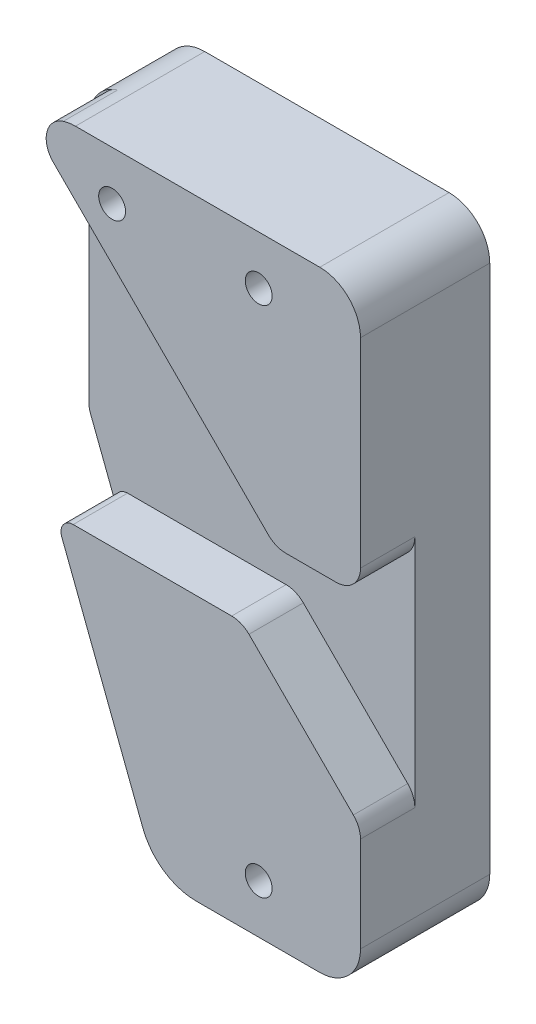
SolidWorks part; units mm, degrees
ref_plane "Front Plane" through (0, 0, 0) normal (0, 0, 1) x (1, 0, 0)
ref_plane "Top Plane" through (0, 0, 0) normal (0, 1, 0) x (1, 0, 0)
ref_plane "Right Plane" through (0, 0, 0) normal (1, 0, 0) x (0, 0, -1)
sketch "Sketch1" plane through (0, 0, 0) normal (0, 0, 1) x (1, 0, 0)
  line L0 (12.5, 69) -> (12.5, 6) construction
  line L1 (0, 0) -> (25, 0)
  line L2 (0, 0) -> (0, 75)
  line L3 (0, 75) -> (25, 75)
  line L4 (25, 0) -> (25, 75)
  line L6 (0, 75) -> (-15, 75)
  line L7 (0, 75) -> (0, 37.5)
  line L8 (0, 37.5) -> (-15, 37.5)
  line L9 (-15, 75) -> (-15, 37.5)
  circle A0 centre (12.5, 69) radius 1.5
  circle A1 centre (12.5, 6) radius 1.5
  circle A2 centre (12.5, 37.5) radius 1.5
  dimension "D3" = 3
  dimension "D4" = 3
  dimension "D7" = 3
  dimension "D1" = 75
  dimension "D2" = 25
  dimension "D5" = 6
  dimension "D6" = 6
  dimension "D8" = 0
  dimension "D9" = 12.5
  dimension "D10" = 15
extrude "Boss-Extrude1" add sketch "Sketch1" along normal blind 2.85 contours L6 L9 L8 L2 | L1 L4 L3 L2 A0 A2 A1 region at (0.7906, 18.75, 0) region at (-7.5, 56.25, 0)
fillet "Fillet1" radius 5 5 edges at (25, 0, 1.425) (0, 0, 1.425) (25, 75, 1.425) (-15, 75, 1.425) (0, 37.5, 1.425)
fillet "Fillet2" radius 2 1 edges at (-15, 37.5, 1.425)
sketch "Sketch5" plane through (0, 0, 2.85) normal (0, 0, 1) x (1, 0, 0)
  line L0 (0, 25) -> (25, 50)
  line L3 (-17.5, 42.5) -> (42.5, 42.5)
  line L4 (42.5, 32.5) -> (42.5, 42.5)
  line L5 (-0.8417, 35.2764) -> (42.5, 42.5) construction
  line L6 (-17.5, 42.5) -> (42.5, 32.5) construction
  line L7 (0, 17.9289) -> (25, 42.9289)
  line L8 (0, 32.0711) -> (21.4645, 53.5355)
  line L9 (-20.8226, 11.2484) -> (21.4645, 53.5355) construction
  line L10 (-17.2871, 7.7129) -> (25, 50) construction
  line L11 (-13.7516, 4.1774) -> (28.5355, 46.4645) construction
  line L12 (21.4645, 53.5355) -> (25, 57.0711)
  line L13 (-15, 70) -> (-15, 39.5)
  line L14 (-13, 37.5) -> (-5, 37.5)
  line L15 (0, 32.5) -> (0, 5)
  line L16 (5, 0) -> (20, 0)
  line L17 (25, 5) -> (25, 70)
  line L18 (20, 75) -> (-10, 75)
  line L19 (-15, 70) -> (-15, 39.5)
  line L20 (-13, 37.5) -> (-5, 37.5)
  line L21 (0, 32.5) -> (0, 5)
  line L22 (5, 0) -> (20, 0)
  line L23 (25, 5) -> (25, 70)
  line L24 (20, 75) -> (-10, 75)
  line L25 (42.5, 32.5) -> (14.5711, 32.5)
  arc A6 (-15, 39.5) -> (-13, 37.5) centre (-13, 39.5) ccw
  arc A7 (0, 32.5) -> (-5, 37.5) centre (-5, 32.5) ccw
  arc A8 (0, 5) -> (5, 0) centre (5, 5) ccw
  arc A9 (20, 0) -> (25, 5) centre (20, 5) ccw
  arc A10 (25, 70) -> (20, 75) centre (20, 70) ccw
  arc A11 (-10, 75) -> (-15, 70) centre (-10, 70) ccw
  arc A12 (-15, 39.5) -> (-13, 37.5) centre (-13, 39.5) ccw
  arc A13 (0, 32.5) -> (-5, 37.5) centre (-5, 32.5) ccw
  arc A14 (0, 5) -> (5, 0) centre (5, 5) ccw
  arc A15 (20, 0) -> (25, 5) centre (20, 5) ccw
  arc A16 (25, 70) -> (20, 75) centre (20, 70) ccw
  arc A17 (-10, 75) -> (-15, 70) centre (-10, 70) ccw
  point P0 (12.5, 37.5)
  point P9 (12.5, 37.5)
  line M2 (-15, 70) -> (-15, 39.5)
  line M6 (0, 32.5) -> (0, 5)
  arc M7 (0, 5) -> (5, 0) centre (5, 5) ccw
  line M8 (5, 0) -> (20, 0)
  arc M9 (20, 0) -> (25, 5) centre (20, 5) ccw
  line M10 (25, 5) -> (25, 70)
  arc M11 (25, 70) -> (20, 75) centre (20, 70) ccw
  line M12 (20, 75) -> (-10, 75)
  arc M13 (-10, 75) -> (-15, 70) centre (-10, 70) ccw
  circle M15 centre (12.5, 6) radius 1.5
  circle M16 centre (12.5, 69) radius 1.5
  dimension "D3" = 0
  dimension "D4" = 5
  dimension "D5" = 5
extrude "Boss-Extrude2" add sketch "Sketch5" along normal blind 3.5 contours L8 L12 L3 M10 M11 M12 M13 M2 M16 | L25 L7 M10 M6 M7 M8 M9 M15 region at (13.6784, 14.8345, 2.85) region at (3.588, 59.5787, 2.85)
fillet "Fillet3" radius 3.5 2 edges at (14.5711, 32.5, 4.6) (10.4289, 42.5, 4.6)
fillet "Fillet4" radius 2 1 edges at (-15, 42.5, 4.6)
fillet "Fillet5" radius 2 3 edges at (0, 17.9289, 4.6) (25, 32.5, 4.6) (25, 57.0711, 4.6)
sketch "Sketch6" plane through (0, 0, 6.35) normal (0, 0, 1) x (1, 0, 0)
  circle A0 centre (-5.5, 69) radius 1.5
  circle A1 centre (12.5, 69) radius 1.5 construction
  dimension "D1" = 3
  dimension "D2" = 18
extrude "Cut-Extrude1" cut sketch "Sketch6" against normal blind 10
sketch "Sketch8" plane through (0, 0, 0) normal (0, 0, -1) x (-1, 0, 0)
  line L6 (5, 37.5) -> (13, 37.5)
  line L7 (15, 39.5) -> (15, 70)
  line L8 (10, 75) -> (-20, 75)
  line L9 (-25, 70) -> (-25, 5)
  line L10 (-20, 0) -> (-5, 0)
  line L11 (0, 5) -> (0, 32.5)
  line L12 (5, 37.5) -> (13, 37.5)
  line L13 (15, 39.5) -> (15, 70)
  line L14 (10, 75) -> (-20, 75)
  line L15 (-25, 70) -> (-25, 5)
  line L16 (-20, 0) -> (-5, 0)
  line L17 (0, 5) -> (0, 32.5)
  arc A6 (13, 37.5) -> (15, 39.5) centre (13, 39.5) ccw
  arc A7 (15, 70) -> (10, 75) centre (10, 70) ccw
  arc A8 (-20, 75) -> (-25, 70) centre (-20, 70) ccw
  arc A9 (-25, 5) -> (-20, 0) centre (-20, 5) ccw
  arc A10 (-5, 0) -> (0, 5) centre (-5, 5) ccw
  arc A11 (5, 37.5) -> (0, 32.5) centre (5, 32.5) ccw
  arc A12 (13, 37.5) -> (15, 39.5) centre (13, 39.5) ccw
  arc A13 (15, 70) -> (10, 75) centre (10, 70) ccw
  arc A14 (-20, 75) -> (-25, 70) centre (-20, 70) ccw
  arc A15 (-25, 5) -> (-20, 0) centre (-20, 5) ccw
  arc A16 (-5, 0) -> (0, 5) centre (-5, 5) ccw
  arc A17 (5, 37.5) -> (0, 32.5) centre (5, 32.5) ccw
  circle M13 centre (5.5, 69) radius 1.5
  line M14 (5, 37.5) -> (13, 37.5)
  arc M15 (13, 37.5) -> (15, 39.5) centre (13, 39.5) ccw
  line M16 (15, 39.5) -> (15, 70)
  arc M17 (15, 70) -> (10, 75) centre (10, 70) ccw
  line M18 (10, 75) -> (-20, 75)
  arc M19 (-20, 75) -> (-25, 70) centre (-20, 70) ccw
  line M20 (-25, 70) -> (-25, 5)
  arc M21 (-25, 5) -> (-20, 0) centre (-20, 5) ccw
  line M22 (-20, 0) -> (-5, 0)
  arc M23 (-5, 0) -> (0, 5) centre (-5, 5) ccw
  line M24 (0, 5) -> (0, 32.5)
  arc M25 (0, 32.5) -> (5, 37.5) centre (5, 32.5) cw
  circle M26 centre (-12.5, 37.5) radius 1.5
  circle M27 centre (-12.5, 6) radius 1.5
  circle M28 centre (-12.5, 69) radius 1.5
  dimension "D1" = 0
extrude "Boss-Extrude3" add sketch "Sketch8" along normal blind 6.35 contours M25 M14 M15 M16 M17 M18 M19 M20 M21 M22 M23 M24 M27 M28 M26 M13 region at (7.8634, 41.813, 0)
sketch "Sketch9" plane through (0, 0, 6.35) normal (0, 0, 1) x (1, 0, 0)
  line L0 (13.5459, 31.4749) -> (0.5858, 18.5147) construction
  line L1 (0, 17.1005) -> (0, 5) construction
  line L2 (5, 0) -> (20, 0) construction
  line L3 (25, 5) -> (25, 30.5) construction
  line L4 (23, 32.5) -> (16.0208, 32.5) construction
  line L5 (11.4541, 43.5251) -> (24.4142, 56.4853) construction
  line L6 (25, 57.8995) -> (25, 70) construction
  line L7 (20, 75) -> (-10, 75) construction
  line L8 (-15, 70) -> (-15, 44.5) construction
  line L9 (-13, 42.5) -> (8.9792, 42.5) construction
  line L10 (13.5459, 31.4749) -> (0.5858, 18.5147)
  line L11 (0, 17.1005) -> (0, 5)
  line L12 (5, 0) -> (20, 0)
  line L13 (25, 5) -> (25, 30.5)
  line L14 (23, 32.5) -> (16.0208, 32.5)
  line L15 (11.4541, 43.5251) -> (24.4142, 56.4853)
  line L16 (25, 57.8995) -> (25, 70)
  line L17 (20, 75) -> (-10, 75)
  line L18 (-15, 70) -> (-15, 44.5)
  line L19 (-13, 42.5) -> (8.9792, 42.5)
  arc A0 (0.5858, 18.5147) -> (0, 17.1005) centre (2, 17.1005) ccw construction
  arc A1 (0, 5) -> (5, 0) centre (5, 5) ccw construction
  arc A2 (20, 0) -> (25, 5) centre (20, 5) ccw construction
  arc A3 (25, 30.5) -> (23, 32.5) centre (23, 30.5) ccw construction
  arc A4 (16.0208, 32.5) -> (13.5459, 31.4749) centre (16.0208, 29) ccw construction
  arc A5 (24.4142, 56.4853) -> (25, 57.8995) centre (23, 57.8995) ccw construction
  arc A6 (25, 70) -> (20, 75) centre (20, 70) ccw construction
  arc A7 (-10, 75) -> (-15, 70) centre (-10, 70) ccw construction
  arc A8 (-15, 44.5) -> (-13, 42.5) centre (-13, 44.5) ccw construction
  arc A9 (8.9792, 42.5) -> (11.4541, 43.5251) centre (8.9792, 46) ccw construction
  arc A10 (0.5858, 18.5147) -> (0, 17.1005) centre (2, 17.1005) ccw
  arc A11 (0, 5) -> (5, 0) centre (5, 5) ccw
  arc A12 (20, 0) -> (25, 5) centre (20, 5) ccw
  arc A13 (25, 30.5) -> (23, 32.5) centre (23, 30.5) ccw
  arc A14 (16.0208, 32.5) -> (13.5459, 31.4749) centre (16.0208, 29) ccw
  arc A15 (24.4142, 56.4853) -> (25, 57.8995) centre (23, 57.8995) ccw
  arc A16 (25, 70) -> (20, 75) centre (20, 70) ccw
  arc A17 (-10, 75) -> (-15, 70) centre (-10, 70) ccw
  arc A18 (-15, 44.5) -> (-13, 42.5) centre (-13, 44.5) ccw
  arc A19 (8.9792, 42.5) -> (11.4541, 43.5251) centre (8.9792, 46) ccw
  circle M1 centre (-5.5, 69) radius 1.5
  circle M2 centre (12.5, 69) radius 1.5
  line M3 (11.4541, 43.5251) -> (24.4142, 56.4853)
  arc M4 (24.4142, 56.4853) -> (25, 57.8995) centre (23, 57.8995) ccw
  line M5 (25, 57.8995) -> (25, 70)
  arc M6 (25, 70) -> (20, 75) centre (20, 70) ccw
  line M7 (20, 75) -> (-10, 75)
  arc M8 (-10, 75) -> (-15, 70) centre (-10, 70) ccw
  line M9 (-15, 70) -> (-15, 44.5)
  arc M10 (-15, 44.5) -> (-13, 42.5) centre (-13, 44.5) ccw
  line M11 (-13, 42.5) -> (8.9792, 42.5)
  arc M12 (8.9792, 42.5) -> (11.4541, 43.5251) centre (8.9792, 46) ccw
extrude "Boss-Extrude4" add sketch "Sketch9" along normal blind 3.175 contours M12 M3 M4 M5 M6 M7 M8 M9 M10 M11 M2 M1 | L14 A14 L10 A10 L11 A11 L12 A12 L13 A13 region at (13.6542, 14.7163, 6.35) region at (3.6533, 59.5379, 6.35)
sketch "Sketch10" plane through (0, 0, 9.525) normal (0, 0, 1) x (1, 0, 0)
  line L1 (25, 57.8995) -> (-15, 57.8995)
  line L2 (25, 57.8995) -> (25, 42.5)
  line L3 (25, 42.5) -> (-15, 42.5)
  line L4 (-15, 57.8995) -> (-15, 42.5)
  line L5 (25, 32.5) -> (0, 32.5)
  line L6 (25, 32.5) -> (25, 17.1005)
  line L7 (25, 17.1005) -> (0, 17.1005)
  line L8 (0, 32.5) -> (0, 17.1005)
  point P0 (-13, 42.5)
  point P1 (-15, 44.5)
  point P8 (25, 32.5)
extrude "Boss-Extrude5" add sketch "Sketch10" against normal up to surface (6.675 mm away) up to face at (5.4763, 37.3513, 2.85)
sketch "Sketch11" plane through (0, 0, 9.525) normal (0, 0, 1) x (1, 0, 0)
  line L0 (8.9645, 33.9645) -> (0.4289, 42.5)
  line L1 (-15, 42.5) -> (25, 42.5) construction
  line L2 (16.0355, 41.0355) -> (25, 32.0711)
  line L3 (16.0355, 41.0355) -> (-14.6824, 71.7535)
  line L4 (8.9645, 33.9645) -> (25, 17.9289)
  line L5 (0.4289, 42.5) -> (-15, 42.5)
  line L6 (-15, 70) -> (-15, 42.5) construction
  line L7 (-15, 70) -> (-15, 42.5)
  line L8 (25, 5) -> (25, 32.5) construction
  line L9 (25, 17.9289) -> (25, 32.5)
  line L10 (24.2965, 32.7746) -> (25.447, 33.2672)
  line L11 (25.447, 33.2672) -> (25, 32.0711)
  arc A0 (-10, 75) -> (-15, 70) centre (-10, 70) ccw construction
  arc A1 (-14.6824, 71.7535) -> (-15, 70) centre (-10, 70) ccw
  line M2 (-15, 70) -> (-15, 42.5)
  line M3 (-15, 42.5) -> (25, 42.5)
  arc M7 (-10, 75) -> (-15, 70) centre (-10, 70) ccw
extrude "Cut-Extrude2" cut sketch "Sketch11" against normal up to surface (6.675 mm away) contours L3 M3 M7 M2 | L4 L9 L2 L3 L0 M3 | L11 L10 L2 region at (15.7738, 33.2738, 9.525) region at (-5.1378, 52.3468, 9.525) region at (24.9145, 32.7043, 9.525) up to face at (0.3745, 37.8745, 2.85)
sketch "Sketch12" plane through (0, 0, -6.35) normal (0, 0, -1) x (-1, 0, 0)
  line L0 (0, 0) -> (14.8675, 38.7841)
  line L1 (-5, 0) -> (0, 0)
  line L2 (5, 37.5) -> (13, 37.5) construction
  line L3 (0, 5) -> (0, 32.5) construction
  line L4 (5, 37.5) -> (13, 37.5)
  line L5 (0, 5) -> (0, 32.5)
  arc A0 (13, 37.5) -> (15, 39.5) centre (13, 39.5) ccw construction
  arc A1 (13, 37.5) -> (14.8675, 38.7841) centre (13, 39.5) ccw
  arc A2 (-5, 0) -> (0, 5) centre (-5, 5) ccw construction
  arc A3 (5, 37.5) -> (0, 32.5) centre (5, 32.5) ccw construction
  arc A4 (5, 37.5) -> (0, 32.5) centre (5, 32.5) ccw
  arc A5 (-5, 0) -> (0, 5) centre (-5, 5) ccw
extrude "Boss-Extrude6" add sketch "Sketch12" against normal up to surface (9.2 mm away) up to face at (1.286, 42.4818, 2.85)
fillet "Fillet6" radius 7 1 edges at (0, 0, -1.75)
sketch "Sketch13" plane through (0, 0, 9.525) normal (0, 0, 1) x (1, 0, 0)
  line L0 (0, 32.5) -> (0, 5) construction
  line L1 (-1.7229, 4.4944) -> (-14.8675, 38.7841) construction
  line L2 (0, 32.5) -> (0, 5)
  line L3 (-1.7229, 4.4944) -> (-12.4585, 32.5)
  line L4 (0, 32.5) -> (-12.4585, 32.5)
  line L5 (4.8133, 0) -> (5, 0)
  arc A0 (0, 5) -> (5, 0) centre (5, 5) ccw construction
  arc A1 (-1.7229, 4.4944) -> (4.8133, 0) centre (4.8133, 7) ccw construction
  arc A2 (0, 5) -> (5, 0) centre (5, 5) ccw
  arc A3 (-1.7229, 4.4944) -> (4.8133, 0) centre (4.8133, 7) ccw
extrude "Boss-Extrude7" add sketch "Sketch13" against normal up to surface (6.675 mm away) up to face at (1.6689, 30.4168, 2.85)
fillet "Fillet7" radius 3 5 edges at (25, 42.5, 6.1875) (25, 17.9289, 6.1875) (10.4289, 32.5, 6.1875) (14.5711, 42.5, 6.1875) (-14.6824, 71.7535, 6.1875)
fillet "Fillet8" radius 1.5 1 edges at (-12.4585, 32.5, 6.1875)
sketch "Sketch15" plane through (0, 0, -6.35) normal (0, 0, -1) x (-1, 0, 0)
  circle A0 centre (-12.5, 69) radius 1.65
  circle A1 centre (-12.5, 37.5) radius 1.65
  circle A2 centre (-12.5, 6) radius 1.65
  circle A3 centre (5.5, 69) radius 1.65
  dimension "D1" = 3.3
  dimension "D2" = 3.3
  dimension "D3" = 3.3
  dimension "D4" = 3.3
extrude "Cut-Extrude3" cut sketch "Sketch15" against normal through all
